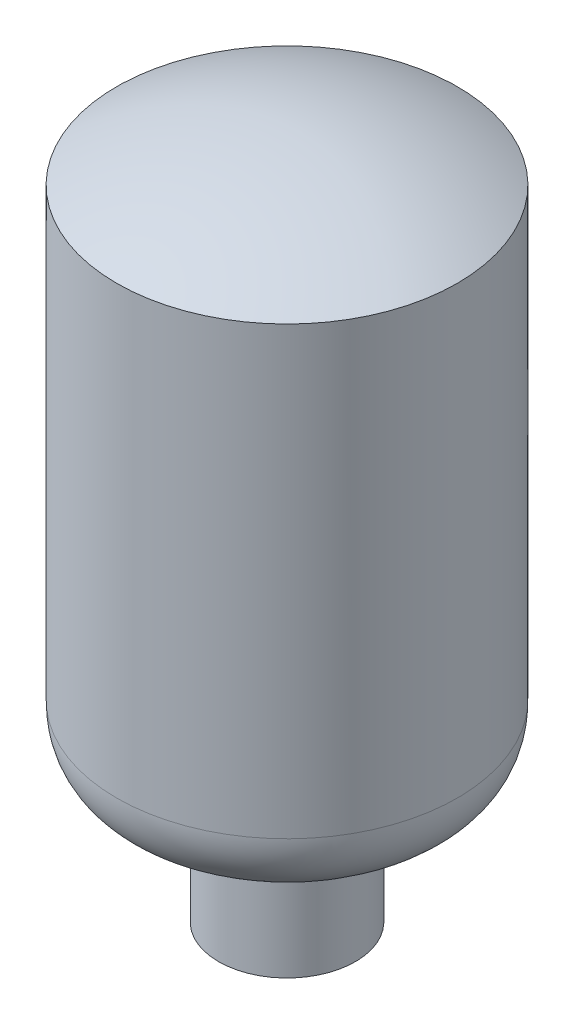
SolidWorks part; units mm, degrees
ref_plane "Front Plane" through (0, 0, 0) normal (0, 0, 1) x (1, 0, 0)
ref_plane "Top Plane" through (0, 0, 0) normal (0, 1, 0) x (1, 0, 0)
ref_plane "Right Plane" through (0, 0, 0) normal (1, 0, 0) x (0, 0, -1)
sketch "Sketch1" plane through (0, 0, 0) normal (0, 1, 0) x (1, 0, 0)
  circle A0 centre (0, 0) radius 21.5
  dimension "D1" = 43
extrude "Boss-Extrude1" add sketch "Sketch1" along normal blind 28
sketch "Sketch2" plane through (0, 0, 0) normal (0, 0, 1) x (1, 0, 0)
  line L0 (0, 0) -> (0, 244.651) construction
  line L1 (21.5, 28) -> (26.7915, 34)
  line L2 (0, 38.5) -> (31.5, 38.5)
  line L3 (0, 60.5) -> (53.5, 60.5)
  line L4 (53.5, 72.7354) -> (53.5, 48.2646) construction
  line L5 (53.5, 60.5) -> (53.5, 200.5)
  line L6 (53.5, 200.5) -> (0, 200.5)
  line L7 (21.5, 28) -> (0, 28)
  line L8 (21.5, 28) -> (-21.5, 28) construction
  line L9 (0, 200.5) -> (0, 28)
  spline S0 degree 2 poles (26.7915, 34) (31.5, 35.2435) (31.5, 38.5) knots 0 0 0 1 1 1
  spline S1 degree 3 poles (31.5, 38.5) (41.8709, 38.4881) (53.5, 45.2057) (53.5, 60.5) knots 0 0 0 0 1 1 1 1
  dimension "D1" = 6
  dimension "D2" = 8
  dimension "D3" = 31.5
  dimension "D4" = 4.5
  dimension "D5" = 22
  dimension "D6" = 53.5
  dimension "D7" = 140
revolve "Revolve1" add sketch "Sketch2" angle 360 about L9 region at (13.5978, 33.6257, 0) region at (24.7948, 50.0622, 0) region at (26.75, 130.5, 0)
sketch "Sketch4" plane through (0, 200.5, 0) normal (0, 1, 0) x (1, 0, 0)
  line L0 (-9.0806, -5.0539) -> (-46.7474, -26.0178)
  line L1 (8.9171, -5.3371) -> (0.1635, 10.391)
  line L2 (0.1635, 10.391) -> (-9.0806, -5.0539)
  line L3 (-9.0806, -5.0539) -> (8.9171, -5.3371)
  line L4 (8.9171, -5.3371) -> (45.9058, -27.4756)
  line L5 (0.1635, 10.391) -> (0, 53.5)
  line L6 (-35.2685, -40.2291) -> (-9.0806, -5.0539)
  line L7 (-52.7758, -8.7729) -> (-9.0806, -5.0539)
  circle A1 centre (0, 0) radius 5.1962 construction
  circle A2 centre (0, 0) radius 53.5 construction
  point P13 (-8.8994, -4.7512)
  dimension "D1" = 18
  dimension "D2" = 18
sketch "Sketch3" plane through (0, 0, 0) normal (0, 0, 1) x (1, 0, 0)
  line L0 (0, 200.5) -> (0, 214.5) construction
  line L1 (53.5, 200.5) -> (-53.5, 200.5) construction
  line L2 (0, 200.5) -> (53.5, 200.5)
  line L3 (0, 214.5) -> (0, 200.5)
  line L4 (-22.1206, 214.5) -> (22.1206, 214.5) construction
  spline S0 degree 2 poles (53.5, 200.5) (27.6507, 214.5) (0, 214.5) knots 0 0 0 1 1 1
  dimension "D1" = 14
revolve "Revolve2" add sketch "Sketch3" angle 360 about L3
shell "Shell2" thickness 1.5 removed face at (0, 0, 21.5)
ref_axis "Axis1" through (0, 269.9089, 0) along (0, -1, 0)
